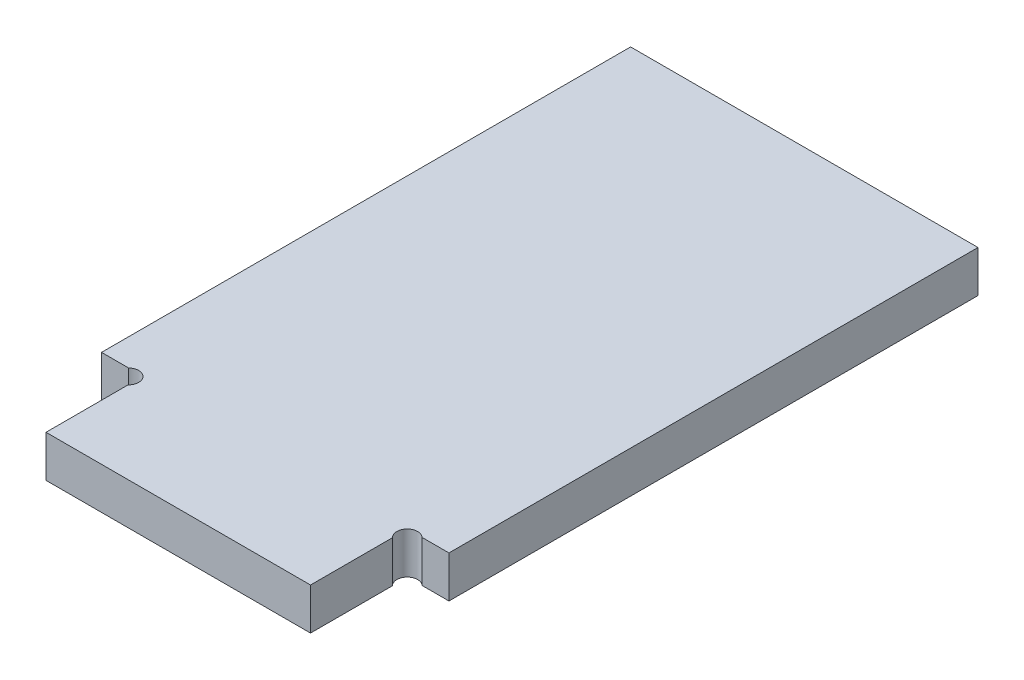
SolidWorks part; units mm, degrees
ref_plane "Front Plane" through (0, 0, 0) normal (0, 0, 1) x (1, 0, 0)
ref_plane "Top Plane" through (0, 0, 0) normal (0, 1, 0) x (1, 0, 0)
ref_plane "Right Plane" through (0, 0, 0) normal (1, 0, 0) x (0, 0, -1)
sketch "Sketch1" plane through (0, 0, 0) normal (0, 1, 0) x (1, 0, 0)
  line L0 (-1.905, -0.2157) -> (-1.905, -1.397)
  line L1 (-1.905, -1.397) -> (1.905, -1.397)
  line L3 (-2.1131, 0) -> (-2.5019, 0)
  line L4 (-2.5019, 0) -> (-2.5019, 7.62)
  line L5 (-2.5019, 7.62) -> (2.5019, 7.62)
  line L6 (0, 7.62) -> (0, -1.397) construction
  line L7 (2.5019, 0) -> (2.5019, 7.62)
  line L8 (2.1131, 0) -> (2.5019, 0)
  line L9 (1.905, -0.2157) -> (1.905, -1.397)
  arc A0 (-1.905, -0.2157) -> (-2.1131, 0) centre (-2.0091, -0.1078) ccw
  arc A1 (1.905, -0.2157) -> (2.1131, 0) centre (2.0091, -0.1078) cw
  point P18 (-1.905, 0)
  dimension "D4" = 0.1499
  dimension "D1" = 3.81
  dimension "D2" = 1.397
  dimension "D3" = 5.0038
  dimension "D5" = 7.62
extrude "Boss-Extrude1" add sketch "Sketch1" along normal mid plane 0.6
